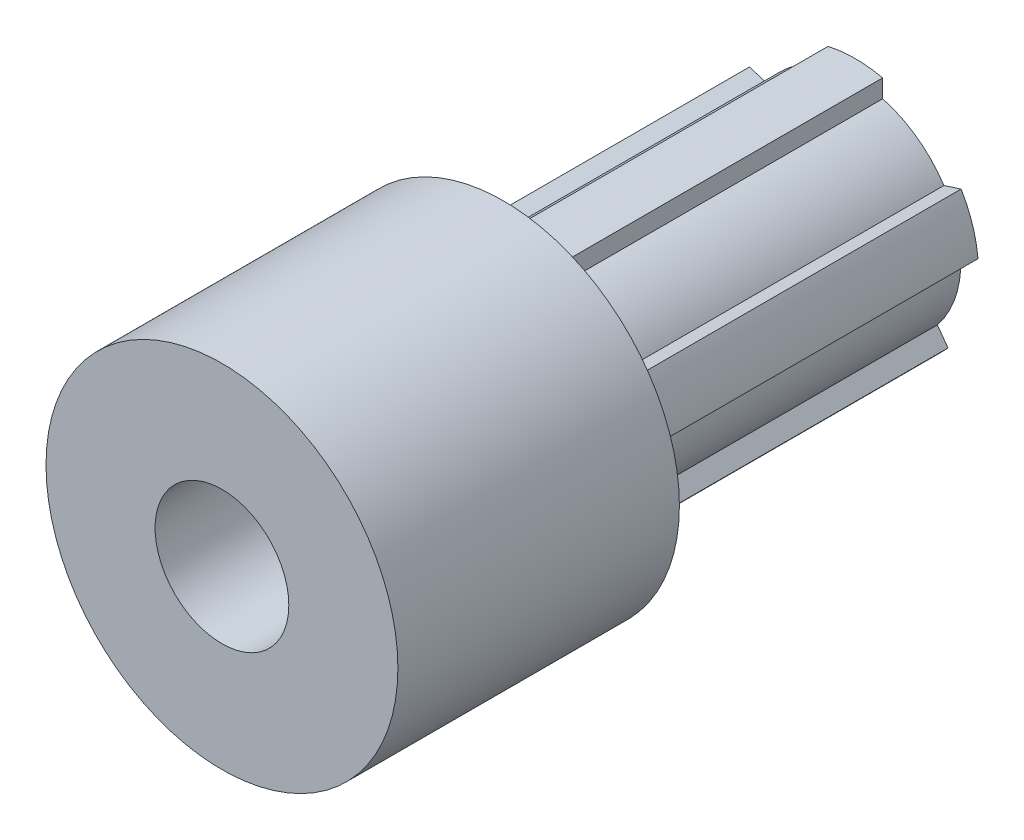
SolidWorks part; units mm, degrees
ref_plane "Front Plane" through (0, 0, 0) normal (0, 0, 1) x (1, 0, 0)
ref_plane "Top Plane" through (0, 0, 0) normal (0, 1, 0) x (1, 0, 0)
ref_plane "Right Plane" through (0, 0, 0) normal (1, 0, 0) x (0, 0, -1)
sketch "Sketch1" plane through (0, 0, 0) normal (0, 0, 1) x (1, 0, 0)
  circle A0 centre (0, 0) radius 25
extrude "Boss-Extrude1" add sketch "Sketch1" along normal blind 90
sketch "Sketch2" plane through (0, 0, 0) normal (0, 0, -1) x (-1, 0, 0)
  line L0 (0, 15) -> (0, 10.569) construction
  line L5 (12.5813, 8.1676) -> (15.0303, 8.9633)
  line L6 (3.88, 14.4895) -> (3.88, 17.0645)
  line L7 (-3.88, 14.4895) -> (-3.88, 17.0645)
  line L8 (14.9793, 0.7874) -> (17.4282, 1.5831)
  line L9 (11.6557, -9.4416) -> (13.1692, -11.5248)
  line L10 (5.3777, -14.0029) -> (6.8912, -16.086)
  line L11 (-5.3777, -14.0029) -> (-6.8912, -16.086)
  line L12 (-11.6557, -9.4416) -> (-13.1692, -11.5248)
  line L13 (-14.9793, 0.7874) -> (-17.4282, 1.5831)
  line L14 (-12.5813, 8.1676) -> (-15.0303, 8.9633)
  arc A0 (3.88, 14.4895) -> (-3.88, 14.4895) centre (0, 0) ccw
  arc A2 (0, 15) -> (3.88, 14.4895) centre (0, 0) cw
  arc A3 (0, 15) -> (-3.88, 14.4895) centre (0, 0) ccw
  circle A4 centre (0, 0) radius 25
  arc A5 (3.88, 17.0645) -> (-3.88, 17.0645) centre (0, 0) ccw
  arc A6 (17.4282, 1.5831) -> (15.0303, 8.9633) centre (0, 0) ccw
  arc A7 (14.9793, 0.7874) -> (12.5813, 8.1676) centre (0, 0) ccw
  arc A8 (6.8912, -16.086) -> (13.1692, -11.5248) centre (0, 0) ccw
  arc A9 (5.3777, -14.0029) -> (11.6557, -9.4416) centre (0, 0) ccw
  arc A10 (-13.1692, -11.5248) -> (-6.8912, -16.086) centre (0, 0) ccw
  arc A11 (-11.6557, -9.4416) -> (-5.3777, -14.0029) centre (0, 0) ccw
  arc A12 (-15.0303, 8.9633) -> (-17.4282, 1.5831) centre (0, 0) ccw
  arc A13 (-12.5813, 8.1676) -> (-14.9793, 0.7874) centre (0, 0) ccw
  circle A14 centre (0, 0) radius 15
  circle A15 centre (0, 0) radius 17.5
  circle M2 centre (0, 0) radius 25
  dimension "D1" = 30
  dimension "D2" = 3.88
  dimension "D3" = 5
  dimension "D5" = 3.88
extrude "Cut-Extrude2" cut sketch "Sketch2" against normal blind 50 contours M2 region at (24.2929, 0, 0)
extrude "Cut-Extrude4" cut sketch "Sketch2<3>" against normal blind 50 contours L7 A15 L14 A14 | L5 A15 L6 A14 | L9 A15 L8 A14 | L11 A15 L10 A14 | L13 A15 L12 A14 region at (-9.3435, 12.8602, 0) region at (-15.1181, -4.9122, 0) region at (9.3435, 12.8602, 0) region at (0, -15.8961, 0) region at (15.1181, -4.9122, 0)
sketch "Sketch2<3>" plane through (0, 0, 0) normal (0, 0, -1) x (-1, 0, 0) same geometry as "Sketch2"
sketch "Sketch3" plane through (0, 0, 90) normal (0, 0, 1) x (1, 0, 0)
  circle A0 centre (0, 0) radius 9.5
extrude "Cut-Extrude5" cut sketch "Sketch3" against normal blind 29.2
ref_plane "Plane1" through (0, 6.68, 0) normal (0, 1, 0) x (1, 0, 0)
sketch "Sketch5" plane through (0, 6.68, 0) normal (0, 1, 0) x (1, 0, 0)
  line L0 (0, -90) -> (0, -85.2) construction
  line L1 (-25, -90) -> (25, -90) construction
  line L2 (0, -85.2) -> (0, -82.2) construction
  line L3 (0, -82.2) -> (0, -57.2) construction
  line L4 (-3, -82.2) -> (-3, -57.2)
  line L5 (3, -82.2) -> (3, -57.2)
  arc A0 (-3, -82.2) -> (3, -82.2) centre (0, -82.2) ccw
  arc A1 (3, -57.2) -> (-3, -57.2) centre (0, -57.2) ccw
  point P5 (0, -69.7)
  dimension "D1" = 3
  dimension "D2" = 6
  dimension "D3" = 25
extrude "Cut-Extrude6" cut sketch "Sketch5" along normal blind 4
